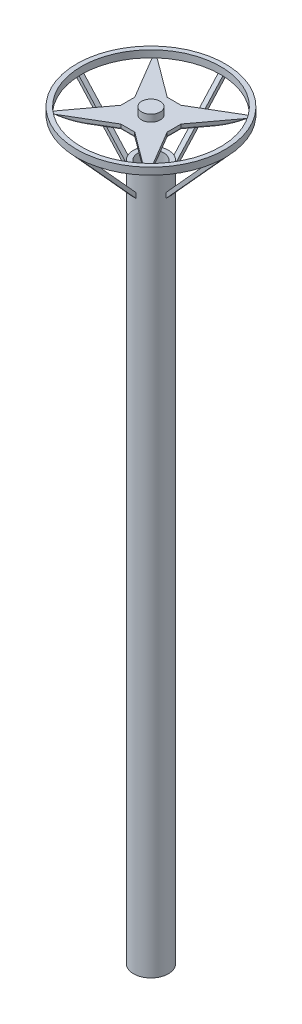
SolidWorks part; units mm, degrees
material "Hexcel AS4C (3000 Filaments)"
ref_plane "Front Plane" through (0, 0, 0) normal (0, 0, 1) x (1, 0, 0)
ref_plane "Top Plane" through (0, 0, 0) normal (0, 1, 0) x (1, 0, 0)
ref_plane "Right Plane" through (0, 0, 0) normal (1, 0, 0) x (0, 0, -1)
ref_plane "Plane1" through (0, 0, 150) normal (0, 0, 1) x (1, 0, 0)
ref_plane "Plane2" through (0, 150, 0) normal (0, 1, 0) x (1, 0, 0)
sketch "Sketch13" plane through (0, 150, 0) normal (0, 1, 0) x (1, 0, 0)
  circle A0 centre (0, -130) radius 7.5
  circle A1 centre (0, -130) radius 5.5
  dimension "D1" = 130
  dimension "D2" = 2
extrude "Boss-Extrude3" add sketch "Sketch13" along normal blind 300 separate body
ref_plane "Plane4" through (0, 465, 0) normal (0, 1, 0) x (1, 0, 0)
sketch "Sketch14" plane through (0, 465, 0) normal (0, 1, 0) x (-1, 0, 0)
  line L1 (-10, 140) -> (10, 140)
  line L2 (-10, 140) -> (-10, 120)
  line L3 (-10, 120) -> (10, 120)
  line L4 (10, 140) -> (10, 120)
  line L5 (-10, 140) -> (10, 120) construction
  line L6 (-10, 120) -> (10, 140) construction
  point P0 (0, 130)
  dimension "D1" = 20
  dimension "D2" = 20
extrude "Boss-Extrude4" add sketch "Sketch14" along normal blind 2
fillet "Fillet3" radius 7 4 edges at (10, 466, 140) (-10, 466, 140) (10, 466, 120) (-10, 466, 120)
sketch "Sketch15" plane through (0, 467, 0) normal (0, 1, 0) x (-1, 0, 0)
  line L4 (10, 127) -> (10, 133) construction
  line L5 (-3, 120) -> (3, 120) construction
  circle A2 centre (0, 130) radius 4
  circle A3 centre (0, 130) radius 30
  circle A4 centre (0, 130) radius 32
  dimension "D1" = 2
  dimension "D3" = 10
  dimension "D6" = 10
extrude "Boss-Extrude5" add sketch "Sketch15" along direction (0, 1, 0) on the side of the normal blind 3 contours A2 | A4 | A3
ref_plane "Plane3" through (0, 0, 0) normal (1, 0, 0) x (0, 0, -1)
sketch "Sketch16" plane through (0, 0, 0) normal (1, 0, 0) x (0, 0, -1)
  line L0 (-122.5, 440) -> (-98, 467)
  line L1 (-122.5, 150) -> (-122.5, 450) construction
  line L2 (-127, 465) -> (-120, 465) construction
  line L3 (-122.5, 442.2041) -> (-100, 467)
  line L4 (-122.5, 440) -> (-122.5, 442.2041)
  line L5 (-98, 467) -> (-100, 467)
  dimension "D1" = 25
extrude "Boss-Extrude6" add sketch "Sketch16" along normal mid plane 2
pattern_circular "CirPattern1" count 4 every 90 about axis through (0, 0, 130) along (0, 1, 0) of "Boss-Extrude6"
sketch "Sketch17" plane through (0, 465, 0) normal (0, 1, 0) x (1, 0, 0)
  line L0 (3, -120) -> (21.48, -109.057)
  line L1 (10, -127) -> (22.5, -110.1569)
  circle A0 centre (0, -130) radius 30 construction
  arc A1 (10, -127) -> (3, -120) centre (3, -127) ccw construction
  arc A2 (10, -127) -> (3, -120) centre (3, -127) ccw
  arc A3 (22.5, -110.1569) -> (21.48, -109.057) centre (0, -130) ccw
  point P15 (21.2557, -108.8293)
  dimension "D1" = 1.5
  dimension "D2" = 22.5
extrude "Boss-Extrude7" add sketch "Sketch17" along normal blind 2
pattern_circular "CirPattern2" count 4 every 90 about axis through (0, 0, 130) along (0, 1, 0) of "Boss-Extrude7"
fillet "Fillet7" radius 30 12 edges at (21.9969, 465, 109.6006) (22.5, 466, 110.1569) (21.48, 466, 109.057) (20.3994, 465, 151.9969) (19.8431, 466, 152.5) (20.943, 466, 151.48) (-21.9969, 465, 150.3994) (-22.5, 466, 149.8431) (-21.48, 466, 150.943) (-20.3994, 465, 108.0031) (-19.8431, 466, 107.5) (-20.943, 466, 108.52)
fillet "Fillet8" radius 0.5 20 edges at (-18.6063, 466.4667, 108.4179) (21.5821, 466.4667, 111.3937) (-21.5821, 466.4667, 148.6063) (18.6063, 466.4667, 151.5821) (10, 465, 130) (-10, 465, 130) (0, 465, 120) (0, 465, 140) (12.926, 465, 123.0573) (6.9427, 465, 142.926) (-12.926, 465, 136.9427) (-6.9427, 465, 117.074) (-12.5995, 465, 122.61) (12.5995, 465, 137.39) (-7.39, 465, 142.5995) (7.39, 465, 117.4005)
